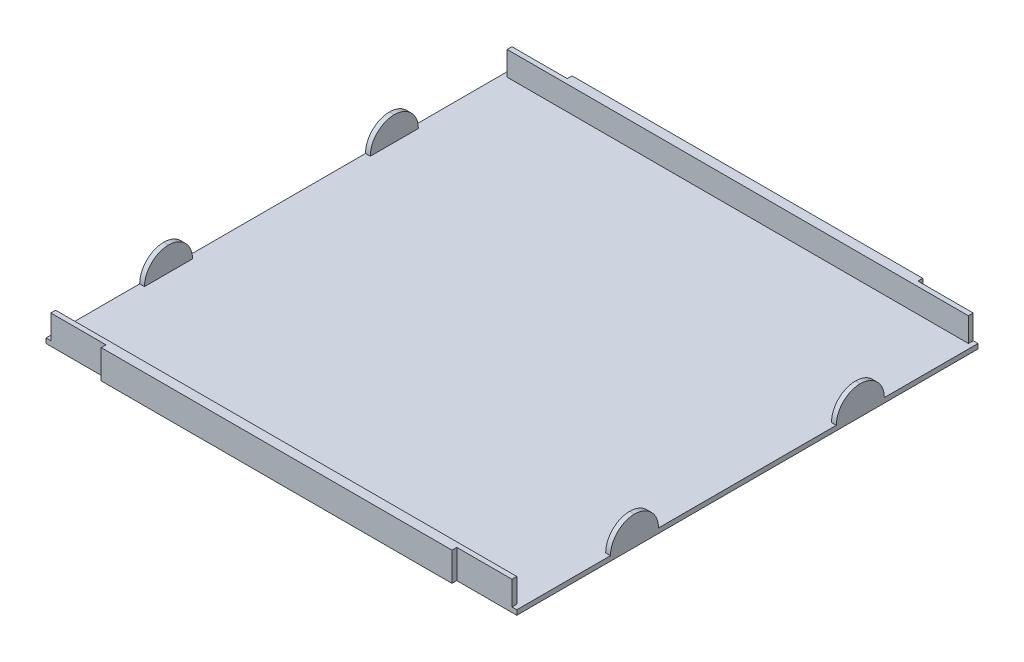
SolidWorks part; units mm, degrees
material "7075-O (SS)"
ref_plane "Front Plane" through (0, 0, 0) normal (0, 0, 1) x (1, 0, 0)
ref_plane "Top Plane" through (0, 0, 0) normal (0, 1, 0) x (1, 0, 0)
ref_plane "Right Plane" through (0, 0, 0) normal (1, 0, 0) x (0, 0, -1)
sketch "Sketch1" plane through (0, 0, 0) normal (0, 1, 0) x (1, 0, 0)
  line L1 (0, 0) -> (98, 0)
  line L2 (0, 0) -> (0, 96)
  line L3 (0, 96) -> (98, 96)
  line L4 (98, 0) -> (98, 96)
  line L5 (12.5, 96) -> (85.5, 96)
  line L6 (12.5, 96) -> (12.5, 97)
  line L7 (12.5, 97) -> (85.5, 97)
  line L8 (85.5, 96) -> (85.5, 97)
  line L9 (12.5, 0) -> (85.5, 0)
  line L10 (12.5, 0) -> (12.5, -1)
  line L11 (12.5, -1) -> (85.5, -1)
  line L12 (85.5, 0) -> (85.5, -1)
  dimension "D1" = 96
  dimension "D2" = 98
  dimension "D3" = 1
  dimension "D4" = 1
  dimension "D5" = 12.5
  dimension "D6" = 12.5
  dimension "D7" = 12.5
  dimension "D8" = 12.5
extrude "Boss-Extrude1" add sketch "Sketch1" along normal blind 1 contours L2 L3 L4 L1 | L11 L12 L9 L10 | L7 L8 L5 L6
sketch "Sketch2" plane through (0, 1, 0) normal (0, 1, 0) x (1, 0, 0)
  line L1 (12.5, -1) -> (85.5, -1)
  line L2 (12.5, -1) -> (12.5, 0)
  line L3 (12.5, 0) -> (85.5, 0)
  line L4 (85.5, -1) -> (85.5, 0)
  line L5 (12.5, 97) -> (85.5, 97)
  line L6 (12.5, 97) -> (12.5, 96)
  line L7 (12.5, 96) -> (85.5, 96)
  line L8 (85.5, 97) -> (85.5, 96)
extrude "Boss-Extrude2" add sketch "Sketch2" along normal blind 5
sketch "Sketch3" plane through (0, 1, 0) normal (0, 1, 0) x (1, 0, 0)
  line L0 (0, 0) -> (0, 96) construction
  line L1 (98, 96) -> (0, 96)
  line L2 (98, 96) -> (98, 95)
  line L3 (98, 95) -> (0, 95)
  line L4 (0, 96) -> (0, 95)
  line L6 (98, 0) -> (0, 0)
  line L7 (98, 0) -> (98, 1)
  line L8 (98, 1) -> (0, 1)
  line L9 (0, 0) -> (0, 1)
  dimension "D1" = 1
  dimension "D2" = 1
extrude "Boss-Extrude3" add sketch "Sketch3" along normal blind 5
sketch "Sketch4" plane through (0, 1, 0) normal (0, 1, 0) x (1, 0, 0)
  line L0 (0, 1) -> (0, 95) construction
  line L1 (0, 76.5) -> (1, 76.5)
  line L2 (0, 76.5) -> (0, 66.5)
  line L3 (0, 66.5) -> (1, 66.5)
  line L4 (1, 76.5) -> (1, 66.5)
  line L5 (98, 1) -> (98, 95) construction
  line L6 (0, 29.5) -> (1, 29.5)
  line L7 (0, 29.5) -> (0, 19.5)
  line L8 (0, 19.5) -> (1, 19.5)
  line L9 (1, 29.5) -> (1, 19.5)
  line L10 (98, 76.5) -> (97, 76.5)
  line L11 (98, 76.5) -> (98, 66.5)
  line L12 (98, 66.5) -> (97, 66.5)
  line L13 (97, 76.5) -> (97, 66.5)
  line L15 (98, 29.5) -> (97, 29.5)
  line L16 (98, 29.5) -> (98, 19.5)
  line L17 (98, 19.5) -> (97, 19.5)
  line L18 (97, 29.5) -> (97, 19.5)
  line L19 (12.5, -1) -> (85.5, -1) construction
  dimension "D1" = 10
  dimension "D2" = 10
  dimension "D3" = 10
  dimension "D4" = 10
  dimension "D5" = 1
  dimension "D6" = 1
  dimension "D7" = 1
  dimension "D8" = 1
  dimension "D9" = 20.5
  dimension "D10" = 20.5
  dimension "D11" = 20.5
  dimension "D12" = 20.5
extrude "Boss-Extrude4" add sketch "Sketch4" along normal blind 5
fillet "Fillet1" radius 5 2 edges at (97.5, 6, -19.5) (97.5, 6, -29.5)
fillet "Fillet2" radius 5 6 edges at (0.5, 6, -29.5) (0.5, 6, -19.5) (0.5, 6, -66.5) (0.5, 6, -76.5) (97.5, 6, -66.5) (97.5, 6, -76.5)
sketch "Sketch5" plane through (0, 6, 0) normal (0, 1, 0) x (1, 0, 0)
  line L0 (98, 1) -> (0, 1) construction
  line L1 (0, 0) -> (1, 0)
  line L2 (0, 0) -> (0, 1)
  line L3 (0, 1) -> (1, 1)
  line L4 (1, 0) -> (1, 1)
  line L5 (98, 96) -> (85.5, 96) construction
  line L6 (98, 0) -> (97, 0)
  line L7 (98, 0) -> (98, 1)
  line L8 (98, 1) -> (97, 1)
  line L9 (97, 0) -> (97, 1)
  line L10 (98, 95) -> (97, 95)
  line L11 (98, 95) -> (98, 96)
  line L12 (98, 96) -> (97, 96)
  line L13 (97, 95) -> (97, 96)
  line L14 (12.5, 96) -> (0, 96) construction
  line L15 (0, 95) -> (1, 95)
  line L16 (0, 95) -> (0, 96)
  line L17 (0, 96) -> (1, 96)
  line L18 (1, 95) -> (1, 96)
  dimension "D1" = 1
  dimension "D2" = 1
  dimension "D3" = 1
  dimension "D4" = 1
extrude "Cut-Extrude1" cut sketch "Sketch5" against normal blind 5
